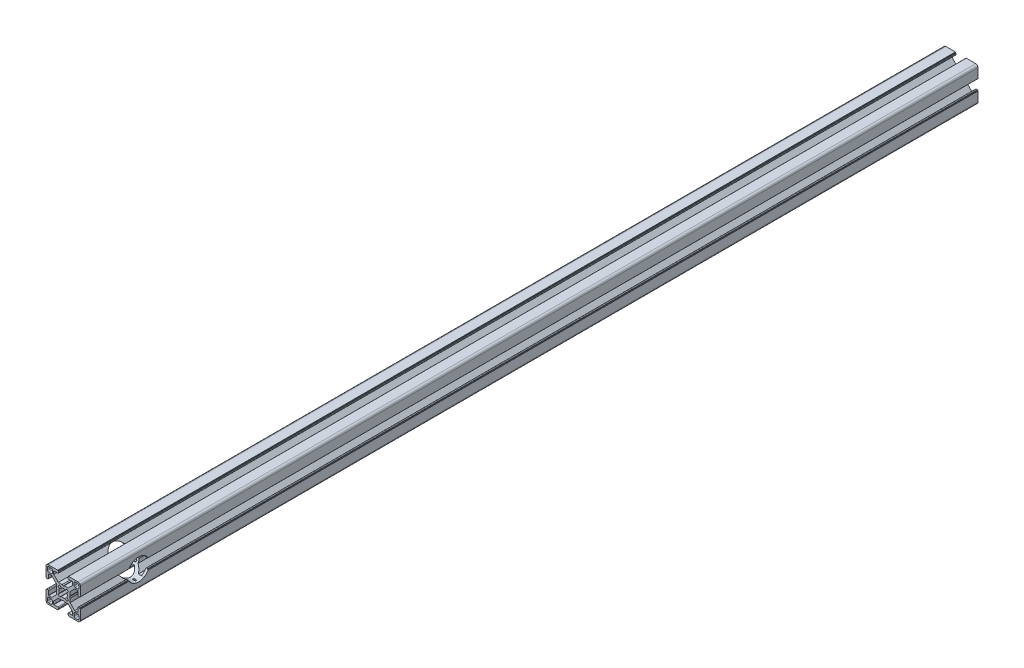
SolidWorks part; units mm, degrees
material "6061 Alloy"
ref_plane "Front" through (0, 0, 0) normal (0, 0, 1) x (1, 0, 0)
ref_plane "Top" through (0, 0, 0) normal (0, 1, 0) x (1, 0, 0)
ref_plane "Right" through (0, 0, 0) normal (1, 0, 0) x (0, 0, -1)
sketch "Sketch1" plane through (0, 0, 0) normal (0, 0, 1) x (1, 0, 0)
  line L0 (13.7, 12.7) -> (13.7, 10.5)
  line L1 (10.5, 9.5) -> (12.7, 9.5)
  line L2 (9.5, 12.7) -> (9.5, 10.5)
  line L3 (10.5, 13.7) -> (12.7, 13.7)
  line L4 (3.1359, 4.5184) -> (1.6001, 3.2806)
  line L5 (3.2806, 1.6001) -> (4.5053, 3.1547)
  line L6 (6.0045, 0.9) -> (5.4849, 0)
  line L7 (6.0045, 4.2045) -> (6.0045, 0.9)
  line L8 (0, -5.4849) -> (0.9, -6)
  line L9 (0.9, -6) -> (4.2045, -6)
  line L10 (4.2045, -6) -> (8.25, -10.05)
  line L11 (8.25, -10.05) -> (8.25, -12.6)
  line L12 (4.65, -12.8) -> (8.05, -12.8)
  line L13 (4.05, -14.3) -> (4.05, -13.4)
  line L14 (4.25, -14.5) -> (4.35, -14.5)
  line L15 (4.55, -14.8) -> (4.55, -14.7)
  line L16 (4.75, -15) -> (13, -15)
  line L17 (15, -13) -> (15, -4.75)
  line L18 (14.7, -4.55) -> (14.8, -4.55)
  line L19 (14.5, -4.35) -> (14.5, -4.25)
  line L20 (13.4, -4.05) -> (14.3, -4.05)
  line L21 (12.8, -8.05) -> (12.8, -4.65)
  line L22 (12.6, -8.25) -> (10.05, -8.25)
  line L23 (10.05, -8.25) -> (6.0045, -4.2045)
  line L24 (6.0045, -4.2045) -> (6.0045, -0.9)
  line L25 (6.0045, -0.9) -> (5.4849, 0)
  line L26 (10.05, 8.25) -> (6.0045, 4.2045)
  line L27 (12.6, 8.25) -> (10.05, 8.25)
  line L28 (12.8, 8.05) -> (12.8, 4.65)
  line L29 (13.4, 4.05) -> (14.3, 4.05)
  line L30 (14.5, 4.35) -> (14.5, 4.25)
  line L31 (14.7, 4.55) -> (14.8, 4.55)
  line L32 (15, 13) -> (15, 4.75)
  line L33 (4.75, 15) -> (13, 15)
  line L34 (4.55, 14.8) -> (4.55, 14.7)
  line L35 (4.25, 14.5) -> (4.35, 14.5)
  line L36 (4.05, 14.3) -> (4.05, 13.4)
  line L37 (4.65, 12.8) -> (8.05, 12.8)
  line L38 (8.25, 10.05) -> (8.25, 12.6)
  line L39 (4.2045, 6) -> (8.25, 10.05)
  line L40 (0.9, 6) -> (4.2045, 6)
  line L41 (0, 5.4849) -> (0.9, 6)
  line L42 (-13.7, -12.7) -> (-13.7, -10.5)
  line L43 (-10.5, -9.5) -> (-12.7, -9.5)
  line L44 (-9.5, -12.7) -> (-9.5, -10.5)
  line L45 (-10.5, -13.7) -> (-12.7, -13.7)
  line L46 (-3.1359, -4.5184) -> (-1.6001, -3.2806)
  line L47 (-3.2806, -1.6001) -> (-4.5053, -3.1547)
  line L48 (0, 5.4849) -> (-0.9, 6)
  line L49 (-0.9, 6) -> (-4.2045, 6)
  line L50 (-4.2045, 6) -> (-8.25, 10.05)
  line L51 (-8.25, 10.05) -> (-8.25, 12.6)
  line L52 (-4.65, 12.8) -> (-8.05, 12.8)
  line L53 (-4.05, 14.3) -> (-4.05, 13.4)
  line L54 (-4.25, 14.5) -> (-4.35, 14.5)
  line L55 (-4.55, 14.8) -> (-4.55, 14.7)
  line L56 (-4.75, 15) -> (-13, 15)
  line L57 (-15, 13) -> (-15, 4.75)
  line L58 (-14.7, 4.55) -> (-14.8, 4.55)
  line L59 (-14.5, 4.35) -> (-14.5, 4.25)
  line L60 (-13.4, 4.05) -> (-14.3, 4.05)
  line L61 (-12.8, 8.05) -> (-12.8, 4.65)
  line L62 (-12.6, 8.25) -> (-10.05, 8.25)
  line L63 (-10.05, 8.25) -> (-6.0045, 4.2045)
  line L64 (-6.0045, -0.9) -> (-5.4849, 0)
  line L65 (-6.0045, -4.2045) -> (-6.0045, -0.9)
  line L66 (-10.05, -8.25) -> (-6.0045, -4.2045)
  line L67 (-12.6, -8.25) -> (-10.05, -8.25)
  line L68 (-12.8, -8.05) -> (-12.8, -4.65)
  line L69 (-13.4, -4.05) -> (-14.3, -4.05)
  line L70 (-14.5, -4.35) -> (-14.5, -4.25)
  line L71 (-14.7, -4.55) -> (-14.8, -4.55)
  line L72 (-15, -13) -> (-15, -4.75)
  line L73 (-4.75, -15) -> (-13, -15)
  line L74 (-4.55, -14.8) -> (-4.55, -14.7)
  line L75 (-4.25, -14.5) -> (-4.35, -14.5)
  line L76 (-4.05, -14.3) -> (-4.05, -13.4)
  line L77 (3.2806, -1.6001) -> (4.5053, -3.1547)
  line L78 (3.1359, -4.5184) -> (1.6001, -3.2806)
  line L79 (-4.65, -12.8) -> (-8.05, -12.8)
  line L80 (-8.25, -10.05) -> (-8.25, -12.6)
  line L81 (-4.2045, -6) -> (-8.25, -10.05)
  line L82 (-0.9, -6) -> (-4.2045, -6)
  line L83 (0, -5.4849) -> (-0.9, -6)
  line L84 (10.5, -13.7) -> (12.7, -13.7)
  line L85 (9.5, -12.7) -> (9.5, -10.5)
  line L86 (10.5, -9.5) -> (12.7, -9.5)
  line L87 (13.7, -12.7) -> (13.7, -10.5)
  line L88 (-6.0045, 4.2045) -> (-6.0045, 0.9)
  line L89 (-6.0045, 0.9) -> (-5.4849, 0)
  line L90 (-3.2806, 1.6001) -> (-4.5053, 3.1547)
  line L91 (-3.1359, 4.5184) -> (-1.6001, 3.2806)
  line L92 (-10.5, 13.7) -> (-12.7, 13.7)
  line L93 (-9.5, 12.7) -> (-9.5, 10.5)
  line L94 (-10.5, 9.5) -> (-12.7, 9.5)
  line L95 (-13.7, 12.7) -> (-13.7, 10.5)
  line L96 (-23.4857, 0) -> (20.9308, 0) construction
  line L97 (0, 17.9563) -> (0, -17.361) construction
  arc A0 (13.7, 12.7) -> (12.7, 13.7) centre (12.7, 12.7) ccw
  arc A1 (12.7, 9.5) -> (13.7, 10.5) centre (12.7, 10.5) ccw
  arc A2 (9.5, 10.5) -> (10.5, 9.5) centre (10.5, 10.5) ccw
  arc A3 (10.5, 13.7) -> (9.5, 12.7) centre (10.5, 12.7) ccw
  arc A4 (1.6001, 3.2806) -> (-1.6001, 3.2806) centre (0, 0) ccw
  arc A5 (8.25, -12.6) -> (8.05, -12.8) centre (8.05, -12.6) cw
  arc A6 (4.65, -12.8) -> (4.05, -13.4) centre (4.65, -13.4) ccw
  arc A7 (4.05, -14.3) -> (4.25, -14.5) centre (4.25, -14.3) ccw
  arc A8 (4.35, -14.5) -> (4.55, -14.7) centre (4.35, -14.7) cw
  arc A9 (4.55, -14.8) -> (4.75, -15) centre (4.75, -14.8) ccw
  arc A10 (13, -15) -> (15, -13) centre (13, -13) ccw
  arc A11 (15, -4.75) -> (14.8, -4.55) centre (14.8, -4.75) ccw
  arc A12 (14.7, -4.55) -> (14.5, -4.35) centre (14.7, -4.35) cw
  arc A13 (14.5, -4.25) -> (14.3, -4.05) centre (14.3, -4.25) ccw
  arc A14 (13.4, -4.05) -> (12.8, -4.65) centre (13.4, -4.65) ccw
  arc A15 (12.8, -8.05) -> (12.6, -8.25) centre (12.6, -8.05) cw
  arc A16 (4.5053, 3.1547) -> (3.1359, 4.5184) centre (0, 0) ccw
  arc A17 (12.8, 8.05) -> (12.6, 8.25) centre (12.6, 8.05) ccw
  arc A18 (13.4, 4.05) -> (12.8, 4.65) centre (13.4, 4.65) cw
  arc A19 (14.5, 4.25) -> (14.3, 4.05) centre (14.3, 4.25) cw
  arc A20 (14.7, 4.55) -> (14.5, 4.35) centre (14.7, 4.35) ccw
  arc A21 (15, 4.75) -> (14.8, 4.55) centre (14.8, 4.75) cw
  arc A22 (13, 15) -> (15, 13) centre (13, 13) cw
  arc A23 (4.55, 14.8) -> (4.75, 15) centre (4.75, 14.8) cw
  arc A24 (4.35, 14.5) -> (4.55, 14.7) centre (4.35, 14.7) ccw
  arc A25 (4.05, 14.3) -> (4.25, 14.5) centre (4.25, 14.3) cw
  arc A26 (4.65, 12.8) -> (4.05, 13.4) centre (4.65, 13.4) cw
  arc A27 (8.25, 12.6) -> (8.05, 12.8) centre (8.05, 12.6) ccw
  arc A28 (-13.7, -12.7) -> (-12.7, -13.7) centre (-12.7, -12.7) ccw
  arc A29 (-12.7, -9.5) -> (-13.7, -10.5) centre (-12.7, -10.5) ccw
  arc A30 (-9.5, -10.5) -> (-10.5, -9.5) centre (-10.5, -10.5) ccw
  arc A31 (-10.5, -13.7) -> (-9.5, -12.7) centre (-10.5, -12.7) ccw
  arc A32 (-4.5053, -3.1547) -> (-3.1359, -4.5184) centre (0, 0) ccw
  arc A33 (-3.2806, 1.6001) -> (-3.2806, -1.6001) centre (0, 0) ccw
  arc A34 (-8.25, 12.6) -> (-8.05, 12.8) centre (-8.05, 12.6) cw
  arc A35 (-4.65, 12.8) -> (-4.05, 13.4) centre (-4.65, 13.4) ccw
  arc A36 (-4.05, 14.3) -> (-4.25, 14.5) centre (-4.25, 14.3) ccw
  arc A37 (-4.35, 14.5) -> (-4.55, 14.7) centre (-4.35, 14.7) cw
  arc A38 (-4.55, 14.8) -> (-4.75, 15) centre (-4.75, 14.8) ccw
  arc A39 (-13, 15) -> (-15, 13) centre (-13, 13) ccw
  arc A40 (-15, 4.75) -> (-14.8, 4.55) centre (-14.8, 4.75) ccw
  arc A41 (-14.7, 4.55) -> (-14.5, 4.35) centre (-14.7, 4.35) cw
  arc A42 (-14.5, 4.25) -> (-14.3, 4.05) centre (-14.3, 4.25) ccw
  arc A43 (-13.4, 4.05) -> (-12.8, 4.65) centre (-13.4, 4.65) ccw
  arc A44 (-12.8, 8.05) -> (-12.6, 8.25) centre (-12.6, 8.05) cw
  arc A45 (-4.5053, 3.1547) -> (-3.1359, 4.5184) centre (0, 0) cw
  arc A46 (-12.8, -8.05) -> (-12.6, -8.25) centre (-12.6, -8.05) ccw
  arc A47 (-13.4, -4.05) -> (-12.8, -4.65) centre (-13.4, -4.65) cw
  arc A48 (-14.5, -4.25) -> (-14.3, -4.05) centre (-14.3, -4.25) cw
  arc A49 (3.2806, 1.6001) -> (3.2806, -1.6001) centre (0, 0) cw
  arc A50 (4.5053, -3.1547) -> (3.1359, -4.5184) centre (0, 0) cw
  arc A51 (1.6001, -3.2806) -> (-1.6001, -3.2806) centre (0, 0) cw
  arc A52 (-14.7, -4.55) -> (-14.5, -4.35) centre (-14.7, -4.35) ccw
  arc A53 (-15, -4.75) -> (-14.8, -4.55) centre (-14.8, -4.75) cw
  arc A54 (-13, -15) -> (-15, -13) centre (-13, -13) cw
  arc A55 (-4.55, -14.8) -> (-4.75, -15) centre (-4.75, -14.8) cw
  arc A56 (10.5, -13.7) -> (9.5, -12.7) centre (10.5, -12.7) cw
  arc A57 (9.5, -10.5) -> (10.5, -9.5) centre (10.5, -10.5) cw
  arc A58 (12.7, -9.5) -> (13.7, -10.5) centre (12.7, -10.5) cw
  arc A59 (13.7, -12.7) -> (12.7, -13.7) centre (12.7, -12.7) cw
  arc A60 (-4.35, -14.5) -> (-4.55, -14.7) centre (-4.35, -14.7) ccw
  arc A61 (-4.05, -14.3) -> (-4.25, -14.5) centre (-4.25, -14.3) cw
  arc A62 (-4.65, -12.8) -> (-4.05, -13.4) centre (-4.65, -13.4) cw
  arc A63 (-8.25, -12.6) -> (-8.05, -12.8) centre (-8.05, -12.6) ccw
  arc A64 (-10.5, 13.7) -> (-9.5, 12.7) centre (-10.5, 12.7) cw
  arc A65 (-9.5, 10.5) -> (-10.5, 9.5) centre (-10.5, 10.5) cw
  arc A66 (-12.7, 9.5) -> (-13.7, 10.5) centre (-12.7, 10.5) cw
  arc A67 (-13.7, 12.7) -> (-12.7, 13.7) centre (-12.7, 12.7) cw
  point P81 (15, 15)
  point P82 (0, 15)
  point P203 (0, -15)
  point P204 (15, -15)
  point P206 (0, 0)
  point P207 (15, 0)
  point P219 (-15, 0)
  point P220 (-15, -15)
  point P221 (-15, 15)
  dimension "D6" = 7.3
  dimension "D7" = 11
  dimension "D1" = 30
  dimension "D2" = 15
  dimension "D3" = 30
  dimension "D4" = 8.1
  dimension "D5" = 9
  dimension "D8" = 8.1
extrude "Boss-Extrude1" add sketch "Sketch1" along normal blind 783.59
sketch "Sketch3" plane through (-15, 0, 0) normal (-1, 0, 0) x (0, 0, 1)
  line L0 (783.59, -15) -> (0, -15) construction
  line L1 (783.59, 13) -> (783.59, 4.75) construction
  circle A0 centre (732.79, 0) radius 9.525
  dimension "D2" = 19.05
  dimension "D3" = 50.8
  dimension "D1" = 15
extrude "Cut-Extrude1" cut sketch "Sketch3" against normal up to next
